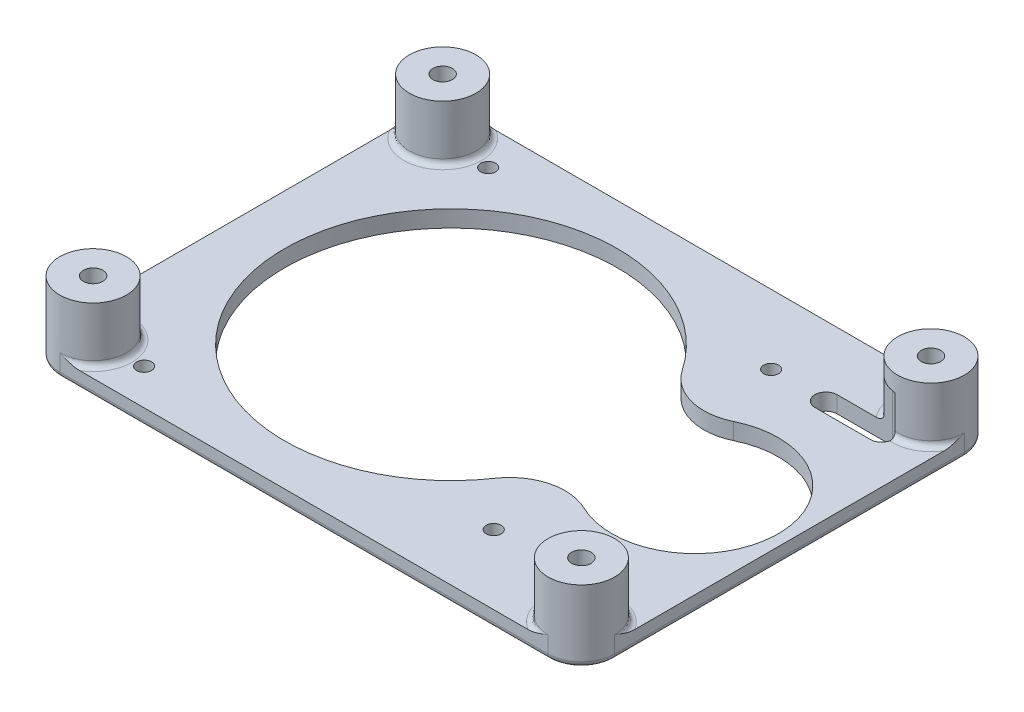
SolidWorks part; units mm, degrees
ref_plane "Спереди" through (0, 0, 0) normal (0, 0, 1) x (1, 0, 0)
ref_plane "Сверху" through (0, 0, 0) normal (0, 1, 0) x (1, 0, 0)
ref_plane "Справа" through (0, 0, 0) normal (1, 0, 0) x (0, 0, -1)
sketch "Эскиз1" plane through (0, 0, 0) normal (0, 1, 0) x (1, 0, 0)
  line L0 (0, 37.5) -> (100, 37.5) construction
  line L17 (0, 0) -> (100, 0)
  line L18 (0, 0) -> (0, 75)
  line L19 (0, 75) -> (100, 75)
  line L20 (100, 0) -> (100, 75)
  line L21 (50, 75) -> (50, 0) construction
  circle A0 centre (14.7, 68.5) radius 1.35
  circle A1 centre (71.7, 62.5) radius 1.35
  circle A2 centre (71.7, 12.5) radius 1.35
  circle A3 centre (14.7, 6.5) radius 1.35
  arc A4 (63.8097, 54.3666) -> (63.8097, 20.6334) centre (39, 37.5) ccw
  arc A5 (76.4477, 24.0068) -> (76.4477, 50.9932) centre (83, 37.5) ccw
  arc A6 (76.4477, 24.0068) -> (63.8097, 20.6334) centre (72.0795, 15.0113) ccw
  arc A7 (63.8097, 54.3666) -> (76.4477, 50.9932) centre (72.0795, 59.9887) ccw
  circle A8 centre (6, 69) radius 1.75
  circle A9 centre (94, 69) radius 1.75
  circle A10 centre (94, 6) radius 1.75
  circle A11 centre (6, 6) radius 1.75
  dimension "D3" = 2.7
  dimension "D8" = 60
  dimension "D9" = 30
  dimension "D10" = 17
  dimension "D12" = 10
  dimension "D15" = 3.5
  dimension "D1" = 75
  dimension "D2" = 100
  dimension "D4" = 62
  dimension "D5" = 50
  dimension "D6" = 57
  dimension "D7" = 28.3
  dimension "D11" = 44
  dimension "D13" = 6
  dimension "D14" = 6
extrude "Бобышка-Вытянуть1" add sketch "Эскиз1" along normal blind 3
fillet "Скругление5" radius 6 4 edges at (100, 1.5, 0) (100, 1.5, -75) (0, 1.5, 0) (0, 1.5, -75)
sketch "Эскиз3" plane through (0, 3, 0) normal (0, 1, 0) x (1, 0, 0)
  line L0 (50, 75) -> (50, 0) construction
  line L1 (94, 75) -> (6, 75) construction
  line L2 (6, 0) -> (94, 0) construction
  line L3 (0, 37.5) -> (100, 37.5) construction
  line L4 (0, 69) -> (0, 6) construction
  line L5 (100, 6) -> (100, 69) construction
  circle A0 centre (6, 69) radius 6
  circle A1 centre (94, 69) radius 6
  circle A2 centre (94, 6) radius 6
  circle A3 centre (6, 6) radius 6
  circle A4 centre (94, 6) radius 1.75 construction
  circle A5 centre (6, 6) radius 1.75 construction
  circle A6 centre (94, 69) radius 1.75 construction
  circle A7 centre (6, 69) radius 1.75 construction
  circle A8 centre (94, 6) radius 1.75
  circle A9 centre (6, 6) radius 1.75
  circle A10 centre (94, 69) radius 1.75
  circle A11 centre (6, 69) radius 1.75
  dimension "D1" = 12
extrude "Бобышка-Вытянуть2" add sketch "Эскиз3" along normal blind 10
fillet "Скругление6" radius 1 12 edges at (1.7574, 0, -1.7574) (0, 0, -37.5) (1.7574, 0, -73.2426) (50, 0, -75) (98.2426, 0, -73.2426) (100, 0, -37.5) (98.2426, 0, -1.7574) (50, 0, 0) (89.7574, 3, -10.2426) (10.2426, 3, -10.2426) (89.7574, 3, -64.7574) (10.2426, 3, -64.7574)
sketch "Эскиз4" plane through (0, 0, 0) normal (0, -1, 0) x (1, 0, 0)
  line L0 (81.5821, -62.5) -> (91.5821, -62.5) construction
  line L1 (81.5821, -60.5) -> (91.5821, -60.5)
  line L2 (81.5821, -64.5) -> (91.5821, -64.5)
  arc A0 (81.5821, -60.5) -> (81.5821, -64.5) centre (81.5821, -62.5) ccw
  arc A1 (91.5821, -64.5) -> (91.5821, -60.5) centre (91.5821, -62.5) ccw
  point P2 (86.5821, -62.5)
  point P7 (81.5821, -62.5)
  dimension "D1" = 4
  dimension "D2" = 10
extrude "Вырез-Вытянуть1" cut sketch "Эскиз4" against normal blind 10
